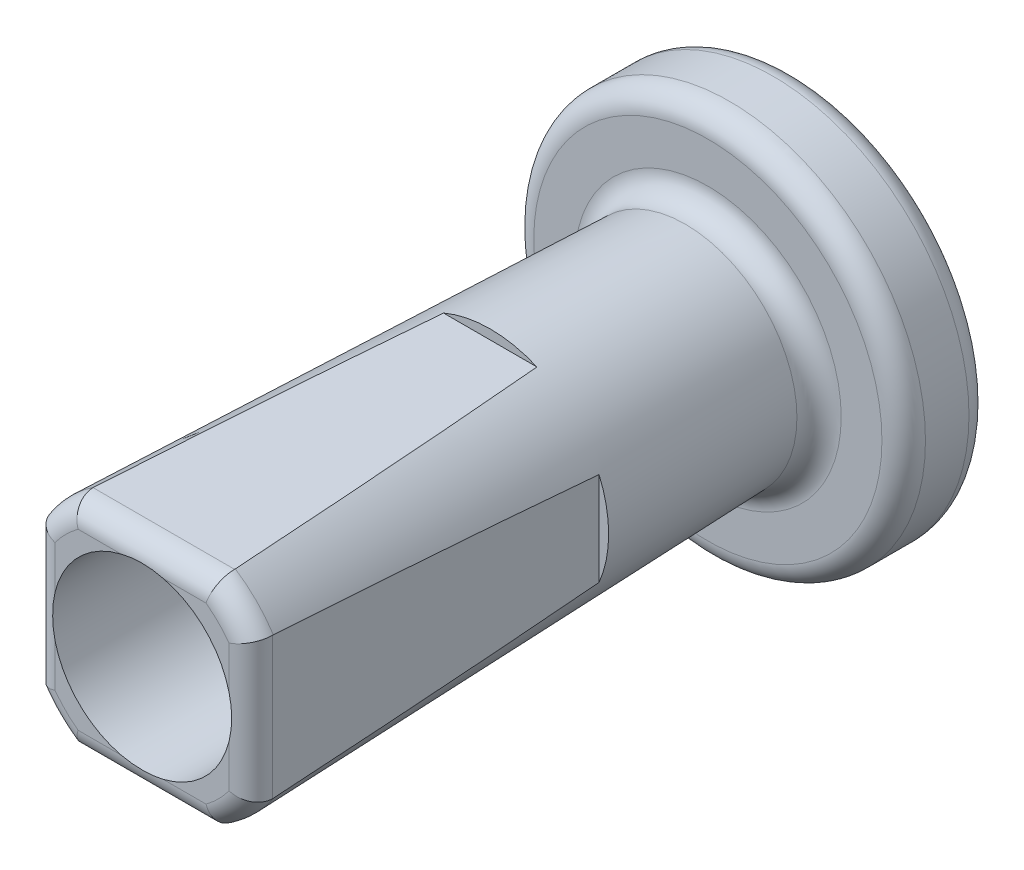
SolidWorks part; units mm, degrees
ref_plane "Спереди" through (0, 0, 0) normal (0, 0, 1) x (1, 0, 0)
ref_plane "Сверху" through (0, 0, 0) normal (0, 1, 0) x (1, 0, 0)
ref_plane "Справа" through (0, 0, 0) normal (1, 0, 0) x (0, 0, -1)
sketch "Эскиз1" plane through (0, 0, 0) normal (0, 0, 1) x (1, 0, 0)
  circle A0 centre (0, 0) radius 4.5
  circle A1 centre (0, 0) radius 2.0571
  dimension "D1" = 9
extrude "Бобышка-Вытянуть1" add sketch "Эскиз1" along normal blind 15
sketch "Эскиз2" plane through (0, 0, 15) normal (0, 0, 1) x (1, 0, 0)
  circle A0 centre (0, 0) radius 3
  dimension "D1" = 6
extrude "Вырез-Вытянуть1" cut sketch "Эскиз2" against normal blind 13 draft 2 flip side to cut draft outward yes
sketch "Эскиз3" plane through (0, 0, 15) normal (0, 0, 1) x (1, 0, 0)
  line L1 (-2.5, 2.5) -> (2.5, 2.5)
  line L2 (-2.5, 2.5) -> (-2.5, -2.5)
  line L3 (-2.5, -2.5) -> (2.5, -2.5)
  line L4 (2.5, 2.5) -> (2.5, -2.5)
  line L5 (-2.5, 2.5) -> (2.5, -2.5) construction
  line L6 (-2.5, -2.5) -> (2.5, 2.5) construction
  point P0 (0, 0)
extrude "Вырез-Вытянуть2" cut sketch "Эскиз3" against normal blind 8 flip side to cut
fillet "Скругление2" radius 0.5 8 edges at (2.1213, -2.1213, 15) (2.5, 0, 15) (2.1213, 2.1213, 15) (0, 2.5, 15) (-2.1213, 2.1213, 15) (-2.5, 0, 15) (-2.1213, -2.1213, 15) (0, -2.5, 15) type face fillet first side face at (2.0571, 0, 15) second side face at (2.5, 0.1463, 11) second side face at (-0.1463, 2.5, 11) second side face at (2.546, 0, 2) second side face at (0.1463, -2.5, 11) second side face at (-2.5, -0.1463, 11)
fillet "Скругление3" radius 0.5 1 edges at (2.546, 0, 2)
fillet "Скругление4" radius 0.5 1 edges at (4.5, 0, 2)
fillet "Скругление5" radius 0.5 1 edges at (4.5, 0, 0)
sketch "Эскиз4" plane through (0, 0, 0) normal (1, 0, 0) x (0, 0, -1)
  line L0 (0, 0) -> (-14.9967, 0)
  spline S0 degree 3 poles (-15, 0.4815) (-15, 0.3225) (-14.9967, 0.1623) (-14.9967, -0.1608) (-15, -0.3247) (-15, -0.4815) knots 0 0 0 0 0.5 0.5 1 1 1 1 construction
